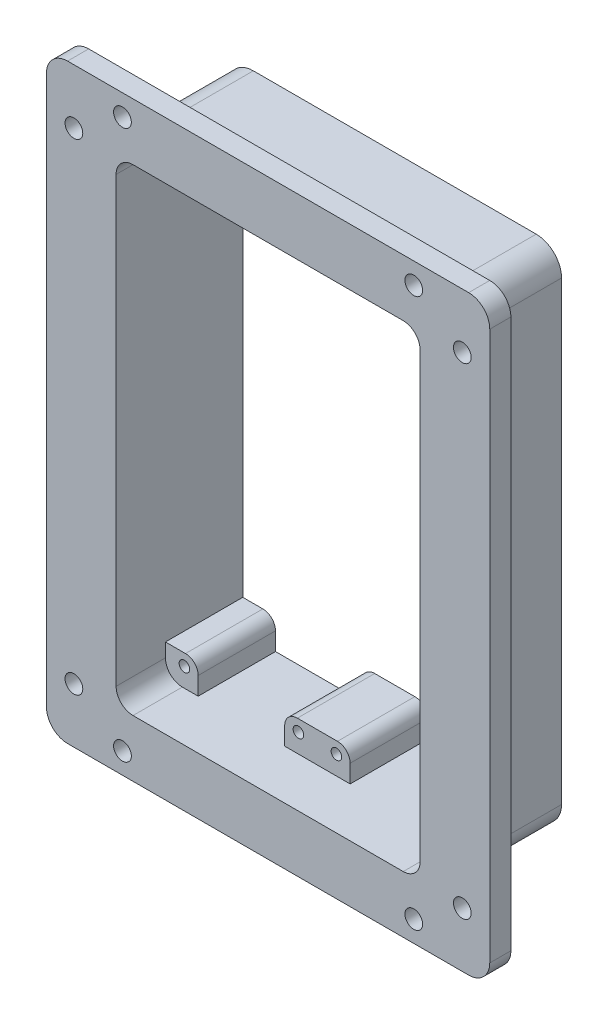
SolidWorks part; units mm, degrees
other "Markup1"
sketch "Sketch3" plane through (50, 70, 5) normal (0.4181, 0.0765, 0.9052) x (0.9081, -0.012, -0.4185)
ref_plane "Front Plane" through (0, 0, 0) normal (0, 0, 1) x (1, 0, 0)
ref_plane "Top Plane" through (0, 0, 0) normal (0, 1, 0) x (1, 0, 0)
ref_plane "Right Plane" through (0, 0, 0) normal (1, 0, 0) x (0, 0, -1)
sketch "Sketch1" plane through (0, 0, 0) normal (0, 0, 1) x (1, 0, 0)
  line L1 (-47.5, 70) -> (47.5, 70)
  line L2 (-52.5, 65) -> (-52.5, -65)
  line L3 (-47.5, -70) -> (47.5, -70)
  line L4 (52.5, 65) -> (52.5, -65)
  line L5 (-52.5, 70) -> (52.5, -70) construction
  line L6 (-52.5, -70) -> (52.5, 70) construction
  line L7 (-32, 56.5) -> (32, 56.5)
  line L8 (-36, 52.5) -> (-36, -52.5)
  line L9 (-32, -56.5) -> (32, -56.5)
  line L10 (36, 52.5) -> (36, -52.5)
  line L11 (-36, 56.5) -> (36, -56.5) construction
  line L12 (-36, -56.5) -> (36, 56.5) construction
  arc A0 (-36, -52.5) -> (-32, -56.5) centre (-32, -52.5) ccw
  arc A1 (32, -56.5) -> (36, -52.5) centre (32, -52.5) ccw
  arc A2 (32, 56.5) -> (36, 52.5) centre (32, 52.5) cw
  arc A3 (-32, 56.5) -> (-36, 52.5) centre (-32, 52.5) ccw
  arc A4 (-52.5, -65) -> (-47.5, -70) centre (-47.5, -65) ccw
  arc A5 (47.5, -70) -> (52.5, -65) centre (47.5, -65) ccw
  arc A6 (47.5, 70) -> (52.5, 65) centre (47.5, 65) cw
  arc A7 (-47.5, 70) -> (-52.5, 65) centre (-47.5, 65) ccw
  point P0 (0, 0)
  point P6 (0, 0)
  dimension "D5" = 4
  dimension "D6" = 5
  dimension "D1" = 105
  dimension "D2" = 140
  dimension "D3" = 113
  dimension "D4" = 72
extrude "Boss-Extrude1" add sketch "Sketch1" along normal blind 5
sketch "Sketch2" plane through (0, 0, 0) normal (0, 0, -1) x (-1, 0, 0)
  line L1 (-33.5, 60) -> (33.5, 60)
  line L2 (-39.5, 54) -> (-39.5, -54)
  line L3 (-33.5, -60) -> (33.5, -60)
  line L4 (39.5, 54) -> (39.5, -54)
  line L5 (-39.5, 60) -> (39.5, -60) construction
  line L6 (-39.5, -60) -> (39.5, 60) construction
  arc A0 (-39.5, -54) -> (-33.5, -60) centre (-33.5, -54) ccw
  arc A1 (33.5, -60) -> (39.5, -54) centre (33.5, -54) ccw
  arc A2 (33.5, 60) -> (39.5, 54) centre (33.5, 54) cw
  arc A3 (-33.5, 60) -> (-39.5, 54) centre (-33.5, 54) ccw
  point P0 (0, 0)
  dimension "D3" = 6
  dimension "D1" = 79
  dimension "D2" = 120
extrude "Boss-Extrude2" add sketch "Sketch2" along normal blind 25
sketch "Sketch4" plane through (0, 0, 5) normal (0, 0, 1) x (1, 0, 0)
  line L0 (47.5, 70) -> (-47.5, 70) construction
  line L1 (52.5, -65) -> (52.5, 65) construction
  line L2 (0, 70) -> (0, -70) construction
  line L3 (-47.5, -70) -> (47.5, -70) construction
  line L4 (0, 0) -> (52.5, 0) construction
  circle A0 centre (34.5, 65) radius 2.1
  circle A1 centre (-34.5, 65) radius 2.1
  circle A2 centre (-34.5, -65) radius 2.1
  circle A3 centre (34.5, -65) radius 2.1
  dimension "D3" = 4.2
  dimension "D1" = 5
  dimension "D2" = 18
extrude "Cut-Extrude1" cut sketch "Sketch4" against normal up to next
sketch "Sketch5" plane through (0, 0, 0) normal (0, 0, 1) x (1, 0, 0)
  line L1 (-32, 56.5) -> (32, 56.5)
  line L2 (-36, 52.5) -> (-36, -52.5)
  line L3 (-32, -56.5) -> (32, -56.5)
  line L4 (36, 52.5) -> (36, -52.5)
  line L5 (-36, 56.5) -> (36, -56.5) construction
  line L6 (-36, -56.5) -> (36, 56.5) construction
  arc A0 (32, -56.5) -> (36, -52.5) centre (32, -52.5) ccw
  arc A1 (-36, -52.5) -> (-32, -56.5) centre (-32, -52.5) ccw
  arc A2 (32, 56.5) -> (36, 52.5) centre (32, 52.5) cw
  arc A3 (-32, 56.5) -> (-36, 52.5) centre (-32, 52.5) ccw
  point P0 (0, 0)
  dimension "D3" = 4
  dimension "D1" = 72
  dimension "D2" = 113
extrude "Cut-Extrude2" cut sketch "Sketch5" against normal up to next
sketch "Sketch8" plane through (0, 0, -25) normal (0, 0, -1) x (-1, 0, 0)
  line L0 (0, 56.5) -> (0, -56.5) construction
  line L1 (-32, 56.5) -> (32, 56.5) construction
  line L2 (32, -56.5) -> (-32, -56.5) construction
  line L3 (-36, 0) -> (0, 0) construction
  line L4 (-36, -52.5) -> (-36, 52.5) construction
  line L5 (28.25, 52.25) -> (28.25, 56.5)
  line L6 (7.75, 56.5) -> (-7.75, 56.5)
  line L7 (0, 56.5) -> (0, 49.25)
  line L8 (4.75, 49.25) -> (-4.75, 49.25)
  line L9 (-7.75, 56.5) -> (-7.75, 52.25)
  line L10 (-36, 49.25) -> (-31.25, 49.25)
  line L11 (-36, 49.25) -> (-36, 52.5)
  line L12 (-32, 56.5) -> (-28.25, 56.5)
  line L13 (-28.25, 52.25) -> (-28.25, 56.5)
  line L14 (32, 56.5) -> (28.25, 56.5)
  line L15 (36, 49.25) -> (36, 52.5)
  line L16 (36, 49.25) -> (31.25, 49.25)
  line L17 (7.75, 56.5) -> (7.75, 52.25)
  line L18 (7.75, -56.5) -> (7.75, -52.25)
  line L19 (36, -49.25) -> (31.25, -49.25)
  line L20 (36, -49.25) -> (36, -52.5)
  line L21 (32, -56.5) -> (28.25, -56.5)
  line L22 (-28.25, -52.25) -> (-28.25, -56.5)
  line L23 (-32, -56.5) -> (-28.25, -56.5)
  line L24 (-36, -49.25) -> (-36, -52.5)
  line L25 (-36, -49.25) -> (-31.25, -49.25)
  line L26 (-7.75, -56.5) -> (-7.75, -52.25)
  line L27 (4.75, -49.25) -> (-4.75, -49.25)
  line L28 (0, -56.5) -> (0, -49.25)
  line L29 (7.75, -56.5) -> (-7.75, -56.5)
  line L30 (28.25, -52.25) -> (28.25, -56.5)
  arc A0 (-36, 52.5) -> (-32, 56.5) centre (-32, 52.5) cw
  arc A1 (-4.75, 49.25) -> (-7.75, 52.25) centre (-4.75, 52.25) cw
  arc A2 (-31.25, 49.25) -> (-28.25, 52.25) centre (-31.25, 52.25) ccw
  arc A3 (31.25, 49.25) -> (28.25, 52.25) centre (31.25, 52.25) cw
  arc A4 (4.75, 49.25) -> (7.75, 52.25) centre (4.75, 52.25) ccw
  arc A5 (36, 52.5) -> (32, 56.5) centre (32, 52.5) ccw
  arc A6 (36, -52.5) -> (32, -56.5) centre (32, -52.5) cw
  arc A7 (4.75, -49.25) -> (7.75, -52.25) centre (4.75, -52.25) cw
  arc A8 (31.25, -49.25) -> (28.25, -52.25) centre (31.25, -52.25) ccw
  arc A9 (-31.25, -49.25) -> (-28.25, -52.25) centre (-31.25, -52.25) cw
  arc A10 (-4.75, -49.25) -> (-7.75, -52.25) centre (-4.75, -52.25) ccw
  arc A11 (-36, -52.5) -> (-32, -56.5) centre (-32, -52.5) ccw
  point P17 (-33.625, 49.25)
  point P22 (-7.75, 49.25)
  point P25 (-28.25, 49.25)
  point P38 (28.25, 49.25)
  point P39 (7.75, 49.25)
  point P65 (7.75, -49.25)
  point P66 (28.25, -49.25)
  point P67 (-28.25, -49.25)
  point P68 (-7.75, -49.25)
  arc M3 (-32, -56.5) -> (-36, -52.5) centre (-32, -52.5) cw
  line M4 (-36, -52.5) -> (-36, 52.5)
  arc M5 (-36, 52.5) -> (-32, 56.5) centre (-32, 52.5) cw
  line M6 (-32, 56.5) -> (32, 56.5)
  arc M7 (32, 56.5) -> (36, 52.5) centre (32, 52.5) cw
  line M8 (36, 52.5) -> (36, -52.5)
  arc M9 (36, -52.5) -> (32, -56.5) centre (32, -52.5) cw
  line M10 (32, -56.5) -> (-32, -56.5)
  dimension "D3" = 4
  dimension "D6" = 3
  dimension "D1" = 7.75
  dimension "D2" = 7.25
  dimension "D4" = 7.75
  dimension "D5" = 7.25
extrude "Boss-Extrude4" add sketch "Sketch8" against normal blind 18.32 contours L10 A2 L13 M6 M5 M4 | A1 L8 L7 L9 M6 | L8 A4 L17 L6 L7 | A3 L16 L5 M8 M7 M6 | A9 L25 L22 M4 M3 M10 | L27 A10 L26 L28 M10 | A7 L27 L28 L18 M10 | L19 A8 L30 M10 M9 M8 region at (-32.0454, 52.8028, -25) region at (-3.7609, 52.9802, -25) region at (3.7609, 52.9802, -25) region at (-32.0454, -52.8028, -25) region at (32.0454, 52.8028, -25) region at (-3.7609, -52.9802, -25) region at (3.7609, -52.9802, -25) region at (32.0454, -52.8028, -25)
sketch "Sketch9" plane through (0, 0, -6.68) normal (0, 0, 1) x (1, 0, 0)
  line L0 (0, 56.5) -> (0, -56.5) construction
  line L1 (32, 56.5) -> (-32, 56.5) construction
  line L2 (-7.75, -56.5) -> (7.75, -56.5) construction
  line L3 (-4.75, 49.25) -> (4.75, 49.25) construction
  line L4 (-7.75, 56.5) -> (-7.75, 52.25) construction
  line L5 (-18, 0) -> (-18, 56.5) construction
  line L7 (0, 0) -> (-36, 0) construction
  line L8 (-36, 52.5) -> (-36, -52.5) construction
  circle A0 centre (-4.5, 52) radius 1.25
  circle A1 centre (-31.5, 52) radius 1.25
  circle A2 centre (31.5, 52) radius 1.25
  circle A3 centre (4.5, 52) radius 1.25
  circle A4 centre (4.5, -52) radius 1.25
  circle A5 centre (31.5, -52) radius 1.25
  circle A6 centre (-31.5, -52) radius 1.25
  circle A7 centre (-4.5, -52) radius 1.25
  dimension "D1" = 2.5
  dimension "D2" = 2.75
  dimension "D3" = 3.25
extrude "Cut-Extrude3" cut sketch "Sketch9" against normal blind 10
sketch "Sketch10" plane through (0, 0, 5) normal (0, 0, 1) x (1, 0, 0)
  line L0 (-52.5, 65) -> (-52.5, -65) construction
  line L1 (47.5, 70) -> (-47.5, 70) construction
  line L2 (0, 70) -> (0, -70) construction
  line L3 (47.5, 70) -> (-47.5, 70) construction
  line L4 (-47.5, -70) -> (47.5, -70) construction
  line L5 (-52.5, 0) -> (52.5, 0) construction
  line L6 (52.5, -65) -> (52.5, 65) construction
  circle A0 centre (-46, 57) radius 2.1
  circle A1 centre (46, 57) radius 2.1
  circle A2 centre (46, -57) radius 2.1
  circle A3 centre (-46, -57) radius 2.1
  dimension "D1" = 4.2
  dimension "D2" = 6.5
  dimension "D3" = 13
extrude "Cut-Extrude4" cut sketch "Sketch10" against normal up to next
